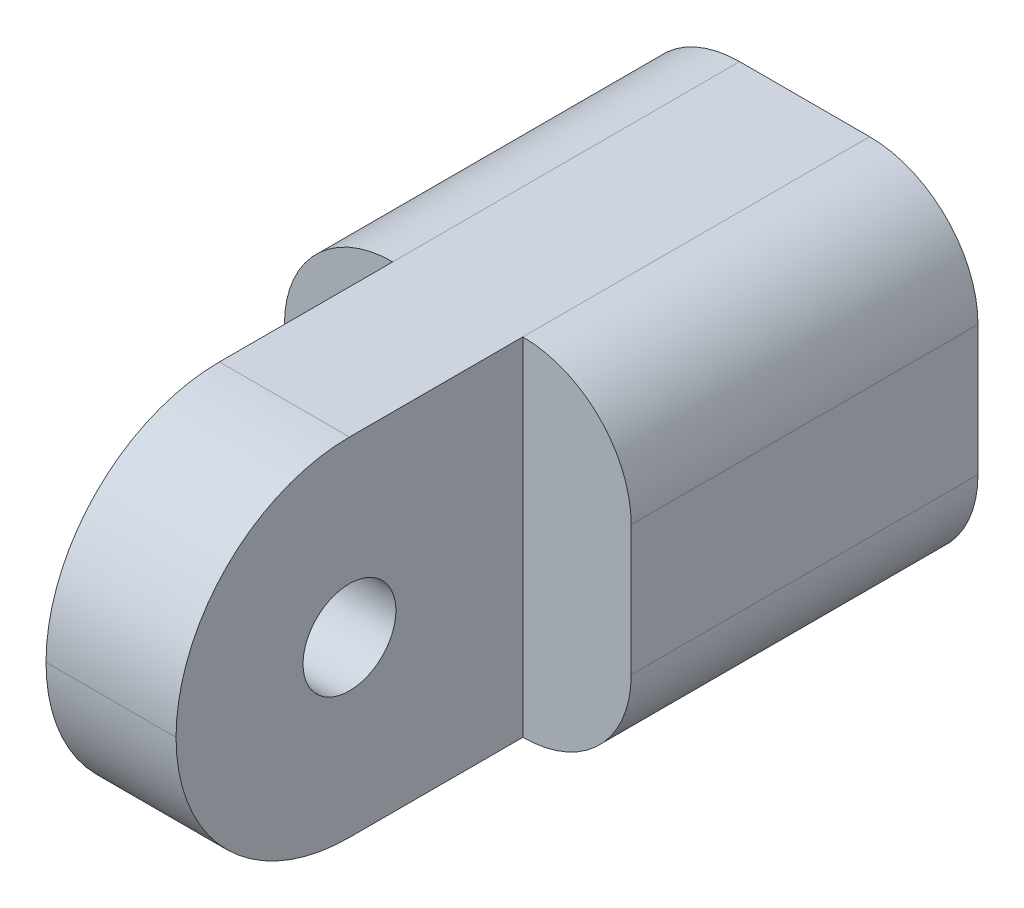
SolidWorks part; units mm, degrees
ref_plane "Front Plane" through (0, 0, 0) normal (0, 0, 1) x (1, 0, 0)
ref_plane "Top Plane" through (0, 0, 0) normal (0, 1, 0) x (1, 0, 0)
ref_plane "Right Plane" through (0, 0, 0) normal (1, 0, 0) x (0, 0, -1)
sketch "Sketch1" plane through (0, 0, 0) normal (0, 0, 1) x (1, 0, 0)
  line L0 (0, -6.35) -> (0, 6.35) construction
  line L5 (-6.35, 6.35) -> (6.35, 6.35)
  line L6 (-6.35, 6.35) -> (-6.35, -6.35)
  line L7 (-6.35, -6.35) -> (6.35, -6.35)
  line L8 (6.35, 6.35) -> (6.35, -6.35)
  point P9 (0, 0)
  dimension "D2" = 12.7
extrude "Boss-Extrude1" add sketch "Sketch1" along normal blind 25.4
fillet "Fillet1" radius 3.9688 4 edges at (6.35, -6.35, 12.7) (-6.35, -6.35, 12.7) (-6.35, 6.35, 12.7) (6.35, 6.35, 12.7)
hole_wizard "Tap Drill for M8x1.25 Tap2" positions "Sketch7" profile "Sketch9" hole size "M8x1.25" standard "ANSI Metric"
sketch "Sketch7" plane through (0, 0, 0) normal (0, 0, -1) x (-1, 0, 0)
  point P0 (0, 0)
sketch "Sketch9" plane through (0, 0, 0) normal (1, 0, 0) x (0, 1, 0)
  line L0 (0, 0) -> (0, 12.0429)
  line L1 (0, 12.0429) -> (3.4, 10)
  line L2 (3.4, 10) -> (3.4, 0)
  line L5 (3.4, 0) -> (0, 0)
  line L10 (0, 12.0429) -> (-3.4, 10) construction
  line L11 (0, -6.35) -> (0, 107.95) construction
  dimension "Hole Dia." = 6.8
  dimension "Hole Depth" = 10
  dimension "Drill Angle" = 118
sketch "Sketch10" plane through (0, 6.35, 0) normal (0, 1, 0) x (1, 0, 0)
  line L0 (-6.35, -25.4) -> (-6.35, 0) construction
  line L1 (-2.3812, -25.4) -> (-6.35, -25.4)
  line L2 (-2.3812, -25.4) -> (-2.3812, -12.7)
  line L3 (-2.3812, -12.7) -> (-6.35, -12.7)
  line L4 (-6.35, -25.4) -> (-6.35, -12.7)
  line L5 (6.35, 0) -> (6.35, -25.4) construction
  line L6 (2.3812, -25.4) -> (6.35, -25.4)
  line L7 (2.3812, -25.4) -> (2.3812, -12.7)
  line L8 (2.3812, -12.7) -> (6.35, -12.7)
  line L9 (6.35, -25.4) -> (6.35, -12.7)
  dimension "D1" = 12.7
  dimension "D2" = 12.7
extrude "Cut-Extrude1" cut sketch "Sketch10" against normal through all both and the other way through all
fillet "Fillet2" radius 6.35 2 edges at (0, -6.35, 25.4) (0, 6.35, 25.4)
hole_wizard "M3 Clearance Hole1" positions "Sketch11" profile "Sketch13" hole size "M3" standard "ANSI Metric" end condition through all
sketch "Sketch11" plane through (-2.3812, 0, 0) normal (-1, 0, 0) x (0, 0, 1)
  point P0 (19.05, 0)
sketch "Sketch13" plane through (-2.3812, 0, 19.05) normal (0, 1, 0) x (0, 0, 1)
  line L0 (0, 0) -> (0, 8.7312)
  line L1 (0, 8.7312) -> (1.7, 8.7312)
  line L2 (1.7, 8.7312) -> (1.7, 0)
  line L5 (1.7, 0) -> (0, 0)
  line L11 (0, -6.35) -> (0, 107.95) construction
  dimension "Thru Hole Dia." = 3.4
  dimension "Thru Hole Depth" = 8.7312
equation "\"D2@Sketch10\"=\"D1@Sketch10\""
